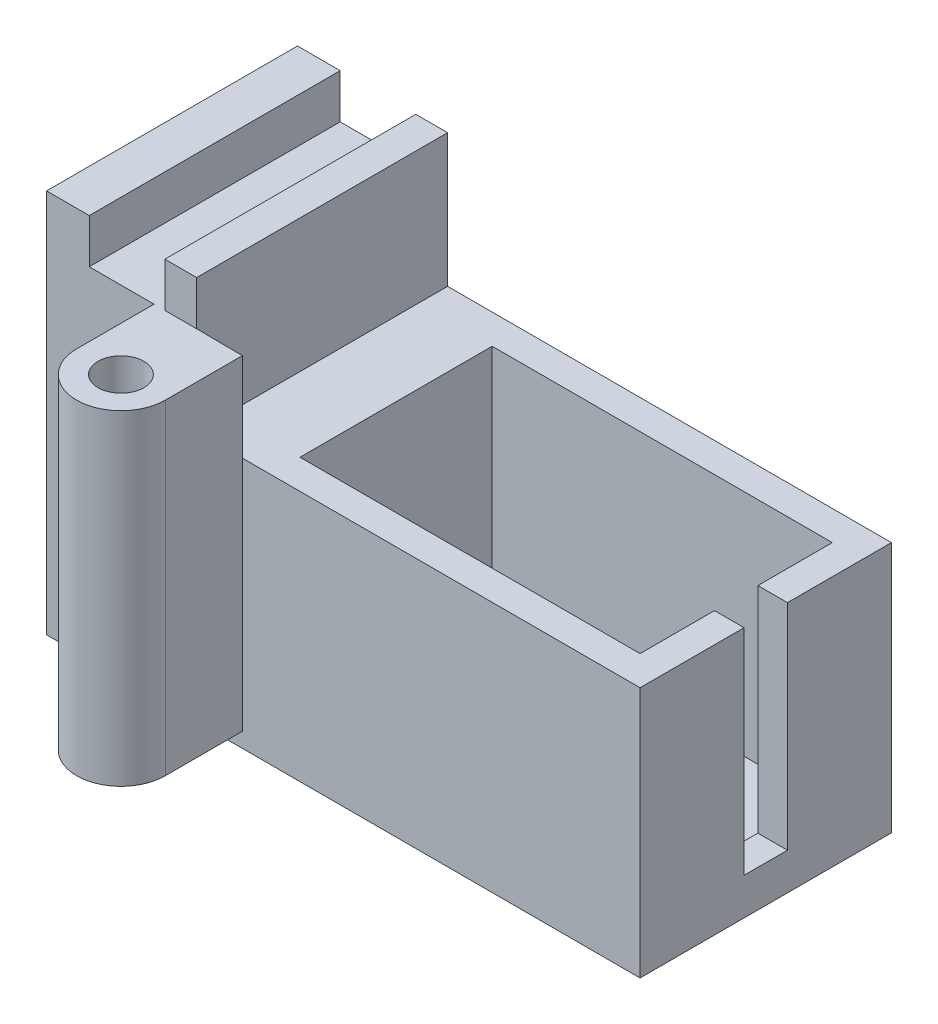
SolidWorks part; units mm, degrees
ref_plane "Front Plane" through (0, 0, 0) normal (0, 0, 1) x (1, 0, 0)
ref_plane "Top Plane" through (0, 0, 0) normal (0, 1, 0) x (1, 0, 0)
ref_plane "Right Plane" through (0, 0, 0) normal (1, 0, 0) x (0, 0, -1)
sketch "Sketch1" plane through (0, 0, 0) normal (0, 1, 0) x (1, 0, 0)
  line L0 (-13.5, 8.5) -> (13.5, 8.5)
  line L1 (-11.5, 6.5) -> (11.5, 6.5)
  line L2 (-11.5, 6.5) -> (-11.5, -6.5)
  line L3 (-11.5, -6.5) -> (11.5, -6.5)
  line L4 (11.5, 6.5) -> (11.5, -6.5)
  line L5 (-11.5, 6.5) -> (11.5, -6.5) construction
  line L6 (-11.5, -6.5) -> (11.5, 6.5) construction
  line L7 (13.5, 8.5) -> (13.5, -8.5)
  line L8 (-13.5, -8.5) -> (13.5, -8.5)
  line L9 (-13.5, 8.5) -> (-13.5, -8.5)
  point P0 (0, 0)
  dimension "D1" = 23
  dimension "D2" = 13
  dimension "D3" = 2
extrude "Boss-Extrude1" add sketch "Sketch1" along normal blind 1.5 contours L4 L1 L2 L3 | L0 L9 L8 L7 L1 L4 L3 L2 region at (0, 0, -8.1809) region at (0, 0, 0)
extrude "Boss-Extrude2" add sketch "Sketch1<3>" along normal blind 17
sketch "Sketch1<3>" plane through (0, 0, 0) normal (0, 1, 0) x (1, 0, 0) same geometry as "Sketch1"
sketch "Sketch2" plane through (0, 17, 0) normal (0, 1, 0) x (1, 0, 0)
  line L1 (10.4748, -1.4667) -> (14.7662, -1.4667)
  line L2 (10.4748, -1.4667) -> (10.4748, 1.4667)
  line L3 (10.4748, 1.4667) -> (14.7662, 1.4667)
  line L4 (14.7662, -1.4667) -> (14.7662, 1.4667)
  line L5 (10.4748, -1.4667) -> (14.7662, 1.4667) construction
  line L6 (10.4748, 1.4667) -> (14.7662, -1.4667) construction
  point P0 (12.6205, 0)
extrude "Cut-Extrude1" cut sketch "Sketch2" against normal blind 14.5
sketch "Sketch3" plane through (0, 1.5, 0) normal (0, 1, 0) x (1, 0, 0)
  circle A0 centre (-6.7654, 0) radius 1.7761
  dimension "D1" = 3.5523
extrude "Cut-Extrude2" cut sketch "Sketch3" against normal blind 14.5
mirror "Mirror1" about plane through (0, 0, 0) normal (1, 0, 0) of "Cut-Extrude2"
sketch "Sketch4" plane through (-13.5, 0, 0) normal (-1, 0, 0) x (0, 0, 1)
  line L4 (-8.5, 0) -> (8.5, 0)
  line L5 (8.5, 0) -> (8.5, 17)
  line L6 (8.5, 17) -> (-8.5, 17)
  line L7 (-8.5, 17) -> (-8.5, 0)
  line L8 (-8.5, 0) -> (8.5, 0)
  line L9 (8.5, 0) -> (8.5, 17)
  line L10 (8.5, 17) -> (-8.5, 17)
  line L11 (-8.5, 17) -> (-8.5, 0)
  dimension "D1" = 0
extrude "Boss-Extrude3" add sketch "Sketch4" along normal blind 5
sketch "Sketch5" plane through (0, 0, 0) normal (0, -1, 0) x (1, 0, 0)
  line L0 (-18.5, -8.5) -> (-18.5, 8.5) construction
  line L1 (-18.5, -8.5) -> (-24.6118, -8.5)
  line L2 (-18.5, -8.5) -> (-18.5, 8.4434)
  line L3 (-18.5, 8.4434) -> (-24.6118, 8.4434)
  line L4 (-24.6118, -8.5) -> (-24.6118, 8.4434)
extrude "Boss-Extrude4" add sketch "Sketch5" against normal up to surface (23 mm away)
sketch "Sketch6" plane through (0, 23, 0) normal (0, 1, 0) x (1, 0, 0)
  line L0 (-19.398, -13.7093) -> (-19.398, -8.4434)
  line L1 (-18.5, -8.4434) -> (-24.6118, -8.4434) construction
  line L2 (-19.398, -8.4434) -> (-13.398, -8.5)
  line L3 (-18.5, -8.5) -> (13.5, -8.5) construction
  line L4 (-13.398, -8.5) -> (-13.398, -13.7093)
  circle A0 centre (-16.398, -13.7093) radius 1.5 construction
  circle A1 centre (-16.398, -13.7093) radius 1.5
  arc A2 (-19.398, -13.7093) -> (-13.398, -13.7093) centre (-16.398, -13.7093) ccw
extrude "Boss-Extrude9" add sketch "Sketch6" against normal blind 22 separate body
sketch "Sketch10" plane through (0, 23, 0) normal (0, 1, 0) x (1, 0, 0)
  line L0 (-13.398, -8.5) -> (-19.398, -8.4434) construction
  line L1 (-26.668, 8.5) -> (-16.5155, 8.5)
  line L2 (-26.668, 8.5) -> (-26.668, -8.4706)
  line L3 (-26.668, -8.4706) -> (-16.5155, -8.4706)
  line L4 (-16.5155, 8.5) -> (-16.5155, -8.4706)
extrude "Boss-Extrude10" add sketch "Sketch10" against normal blind 23 and the other way blind 3
sketch "Sketch8" plane through (0, 26, 0) normal (0, 1, 0) x (1, 0, 0)
  line L0 (-23.7796, -11.5942) -> (-18.6678, -11.5942)
  line L1 (-18.6678, 10.614) -> (-23.7796, 10.614)
  line L2 (-18.6678, 10.614) -> (-18.6678, -11.5942)
  line L4 (-26.668, -8.4706) -> (-19.398, -8.4706)
  line L5 (-16.5155, 8.5) -> (-26.668, 8.5)
  line L6 (-26.668, -8.4706) -> (-19.398, -8.4706)
  line L7 (-19.398, -8.4706) -> (-19.398, -13.7093)
  line L8 (-19.398, -8.4706) -> (-19.398, -13.7093)
  line L9 (-16.5155, 8.5) -> (-26.668, 8.5)
  line L10 (-13.398, -13.7093) -> (-13.398, -8.5)
  line L11 (-13.398, -13.7093) -> (-13.398, -8.5)
  line L12 (-23.7796, 10.614) -> (-23.7796, -11.5942)
  line L13 (-18.6678, 10.614) -> (-23.5428, -11.5942) construction
  line L14 (-18.9162, -11.5942) -> (-23.7796, 10.614) construction
  line L21 (-13.398, -8.5) -> (-16.5155, -8.4706)
  line L22 (-13.398, -8.5) -> (-16.5155, -8.4706)
  line L23 (-16.5155, -8.4706) -> (-16.5155, 8.5)
  line L24 (-16.5155, -8.4706) -> (-16.5155, 8.5)
  line L25 (-26.668, 8.5) -> (-26.668, -8.4706)
  line L26 (-26.668, 8.5) -> (-26.668, -8.4706)
  circle A0 centre (-21.2267, -1.0434) radius 2.5
  arc A2 (-19.398, -13.7093) -> (-13.398, -13.7093) centre (-16.398, -13.7093) ccw
  arc A3 (-19.398, -13.7093) -> (-13.398, -13.7093) centre (-16.398, -13.7093) ccw
  point P6 (-18.7505, -8.6806)
  point P14 (-18.6678, -11.5942)
  dimension "D1" = 0
extrude "Cut-Extrude4" cut sketch "Sketch8" against normal blind 3 and the other way blind 3 contours L1 L12 L0 L2
sketch "Sketch11" plane through (0, 23, 0) normal (0, 1, 0) x (1, 0, 0)
  circle A0 centre (-16.398, -13.7093) radius 1.55
  dimension "D1" = 3.1
extrude "Cut-Extrude5" cut sketch "Sketch11" against normal blind 31
